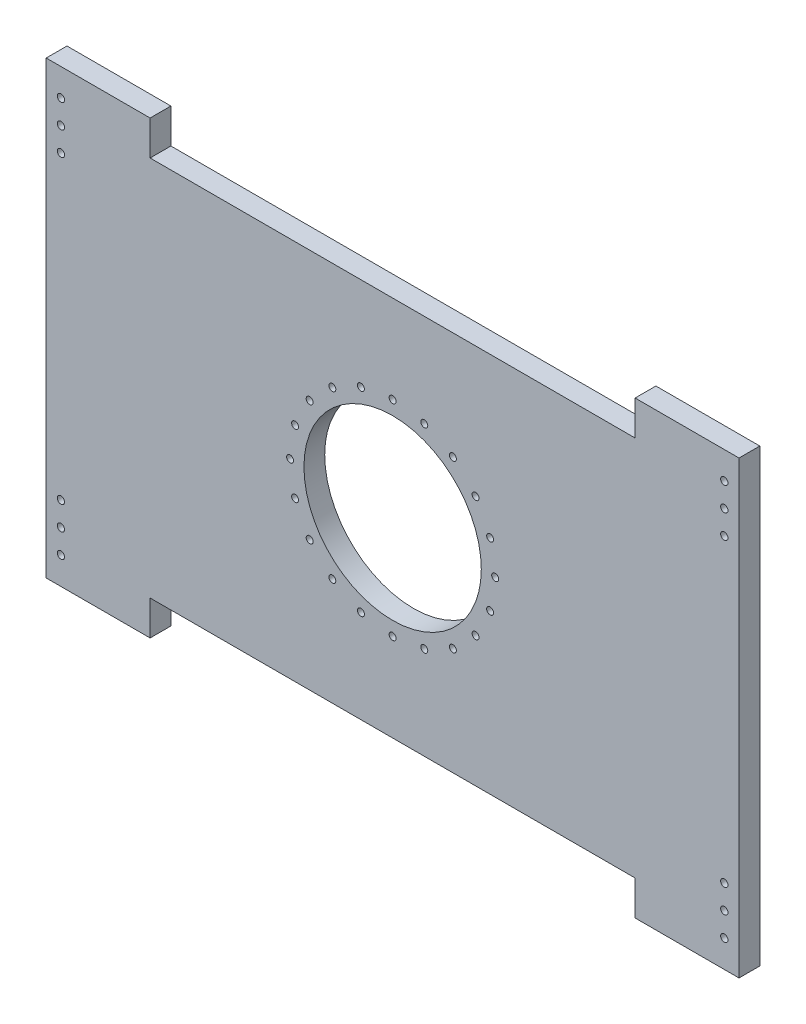
SolidWorks part; units mm, degrees
material "ASTM A36 Acier"
ref_plane "Plan de face" through (0, 0, 0) normal (0, 0, 1) x (1, 0, 0)
ref_plane "Plan de dessus" through (0, 0, 0) normal (0, 1, 0) x (1, 0, 0)
ref_plane "Plan de droite" through (0, 0, 0) normal (1, 0, 0) x (0, 0, -1)
sketch "Esquisse1" plane through (0, 0, 0) normal (0, 0, 1) x (1, 0, 0)
  line L0 (-1000, 1200) -> (-700, 1200)
  line L1 (-700, 1200) -> (-700, 1100)
  line L2 (-700, 1100) -> (700, 1100)
  line L3 (700, 1100) -> (700, 1200)
  line L4 (700, 1200) -> (1000, 1200)
  line L5 (1000, 1200) -> (1000, -100)
  line L6 (1000, -100) -> (700, -100)
  line L7 (700, -100) -> (700, 0)
  line L8 (700, 0) -> (-700, 0)
  line L9 (-700, 0) -> (-700, -100)
  line L10 (-700, -100) -> (-1000, -100)
  line L11 (-1000, -100) -> (-1000, 1200)
  point P15 (0, 0)
  dimension "D1" = 2000
  dimension "D2" = 1300
  dimension "D3" = 1300
  dimension "D4" = 300
  dimension "D5" = 300
  dimension "D6" = 300
  dimension "D7" = 300
  dimension "D8" = 1100
  dimension "D9" = 100
  dimension "D10" = 1400
extrude "Boss.-Extru.1" add sketch "Esquisse1" along normal blind 60
sketch "Esquisse2" plane through (0, 0, 60) normal (0, 0, 1) x (1, 0, 0)
  circle A0 centre (0, 550) radius 256
  dimension "D1" = 512
  dimension "D2" = 550
extrude "Enlèv. mat.-Extru.1" cut sketch "Esquisse2" against normal through all
sketch "Esquisse4" plane through (0, 0, 0) normal (1, 0, 0) x (0, 0, -1)
  line L0 (0, 550) -> (1429.3387, 550) construction
  dimension "D1" = 550
sketch "Esquisse5" plane through (0, 0, 0) normal (0, 0, 1) x (1, 0, 0)
  circle A0 centre (0, 846) radius 10
  circle A1 centre (0, 550) radius 256 construction
  dimension "D1" = 20
  dimension "D2" = 296
extrude "Enlèv. mat.-Extru.3" cut sketch "Esquisse5" along normal through all
pattern_circular "Répétition circulaire1" count 20 every 18 about axis through (0, 550, 0) along (0, 0, -1) of "Enlèv. mat.-Extru.3"
ref_plane "Plan1" through (0, 0, 0) normal (0, 0, -1) x (-1, 0, 0)
sketch "Esquisse6" plane through (0, 0, 0) normal (0, 0, -1) x (-1, 0, 0)
  line L0 (1000, -100) -> (1000, 1200) construction
  line L1 (-1000, -100) -> (-1000, 1200) construction
  line L3 (0, 1100) -> (0, 0) construction
  line L5 (-700, -100) -> (-1000, -100) construction
  line L6 (994.9902, 550) -> (-1002.7622, 550) construction
  line L8 (700, 1100) -> (-700, 1100) construction
  circle A1 centre (-957.5, -21.25) radius 10.5
  circle A8 centre (-957.5, 1121.25) radius 10.5
  circle A9 centre (957.5, 1121.25) radius 10.5
  circle A14 centre (957.5, -21.25) radius 10.5
  circle A15 centre (-957.5, 47.5) radius 10.5
  circle A16 centre (-957.5, 116.25) radius 10.5
  circle A17 centre (-957.5, 983.75) radius 10.5
  circle A18 centre (-957.5, 1052.5) radius 10.5
  circle A19 centre (957.5, 47.5) radius 10.5
  circle A20 centre (957.5, 116.25) radius 10.5
  circle A21 centre (957.5, 1052.5) radius 10.5
  circle A22 centre (957.5, 983.75) radius 10.5
  point P5 (1000, 550)
  point P14 (0, 1100)
  dimension "D2" = 3
  dimension "D9" = 78.75
  dimension "21" = 21
  dimension "D10" = 42.5
extrude "Enlèv. mat.-Extru.4" cut sketch "Esquisse6" against normal through all
ref_plane "Plan2" through (-1000, -100, 60) normal (0, -1, 0) x (-1, 0, 0)
sketch "Esquisse9" plane through (0, 0, 60) normal (0, 0, 1) x (1, 0, 0)
  line L1 (-488.7032, 646.271) -> (-731.9474, 646.271)
  line L2 (-488.7032, 646.271) -> (-488.7032, 825.6293)
  line L3 (-488.7032, 825.6293) -> (-731.9474, 825.6293)
  line L4 (-731.9474, 646.271) -> (-731.9474, 825.6293)
